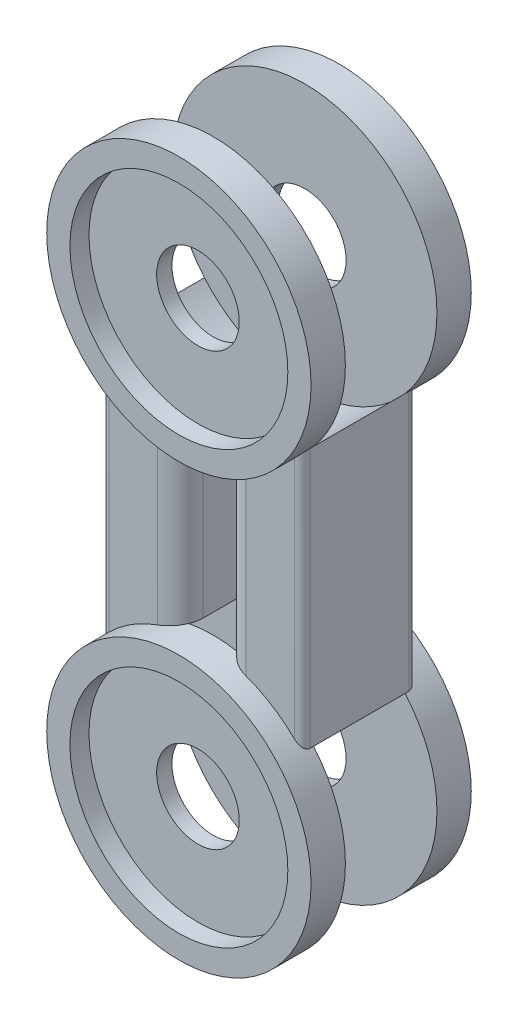
SolidWorks part; units mm, degrees
ref_plane "Front" through (0, 0, 0) normal (0, 0, 1) x (1, 0, 0)
ref_plane "Top" through (0, 0, 0) normal (0, 1, 0) x (1, 0, 0)
ref_plane "Right" through (0, 0, 0) normal (1, 0, 0) x (0, 0, -1)
sketch "Sketch1" plane through (0, 0, 0) normal (0, 0, 1) x (1, 0, 0)
  line L0 (0, 28.286) -> (0, 0) construction
  line L2 (-2.8187, 11.198) -> (-2.8187, 0)
  line L3 (0, 0) -> (2.8187, 0) construction
  line L4 (2.8187, 11.198) -> (2.8187, 0)
  line L5 (2.8187, 0) -> (13.1512, 0)
  line L6 (0, 0) -> (-2.8187, 0) construction
  line L8 (-13.1512, 17.0171) -> (-13.1512, 0)
  line L9 (-13.1512, 0) -> (-2.8187, 0)
  line L10 (13.1512, 17.0171) -> (13.1512, 0)
  circle A0 centre (0, 28.286) radius 17.3189
  circle A1 centre (0, 28.286) radius 14.2787
  circle A2 centre (0, 28.286) radius 5.4117
  point P0 (0.2261, 9.2779)
  point P5 (0.2261, 9.2779)
extrude "Boss-Extrude2" add sketch "Sketch1" against normal mid plane 15 contours A0 L8 L9 L2 | A0 L4 L5 L10 | A0 A1 region at (-8.3492, 6.7547, 0) region at (-8.2581, 13.6225, 0) region at (8.3492, 6.7547, 0)
extrude "Boss-Extrude3" add sketch "Sketch1<4>" along normal mid plane 16 contours A1 A2 region at (-13.8748, 28.286, 0)
sketch "Sketch1<4>" plane through (0, 0, 0) normal (0, 0, 1) x (1, 0, 0) same geometry as "Sketch1"
extrude "Boss-Extrude4" add sketch "Sketch1<5>" along normal mid plane 21 contours A0 A1 region at (-8.2581, 13.6225, 0)
sketch "Sketch1<5>" plane through (0, 0, 0) normal (0, 0, 1) x (1, 0, 0) same geometry as "Sketch1"
extrude "Cut-Extrude2" cut sketch "Sketch1<3>" against normal mid plane 12 contours A0 A1 | A1 A2 region at (-8.2581, 13.6225, 0) region at (-13.8748, 28.286, 0)
sketch "Sketch1<3>" plane through (0, 0, 0) normal (0, 0, 1) x (1, 0, 0) same geometry as "Sketch1"
mirror "Mirror1" about plane through (0, 0, -7.5) normal (0, -1, 0) of "Boss-Extrude4", "Boss-Extrude2", "Cut-Extrude2", "Boss-Extrude3"
fillet "Fillet1" radius 3 4 edges at (2.8187, 0, 7.5) (-2.8187, 0, 7.5) (2.8187, 0, -7.5) (-2.8187, 0, -7.5)
fillet "Fillet2" radius 1 4 edges at (13.1512, 0, -7.5) (-13.1512, 0, -7.5) (13.1512, 0, 7.5) (-13.1512, 0, 7.5)
